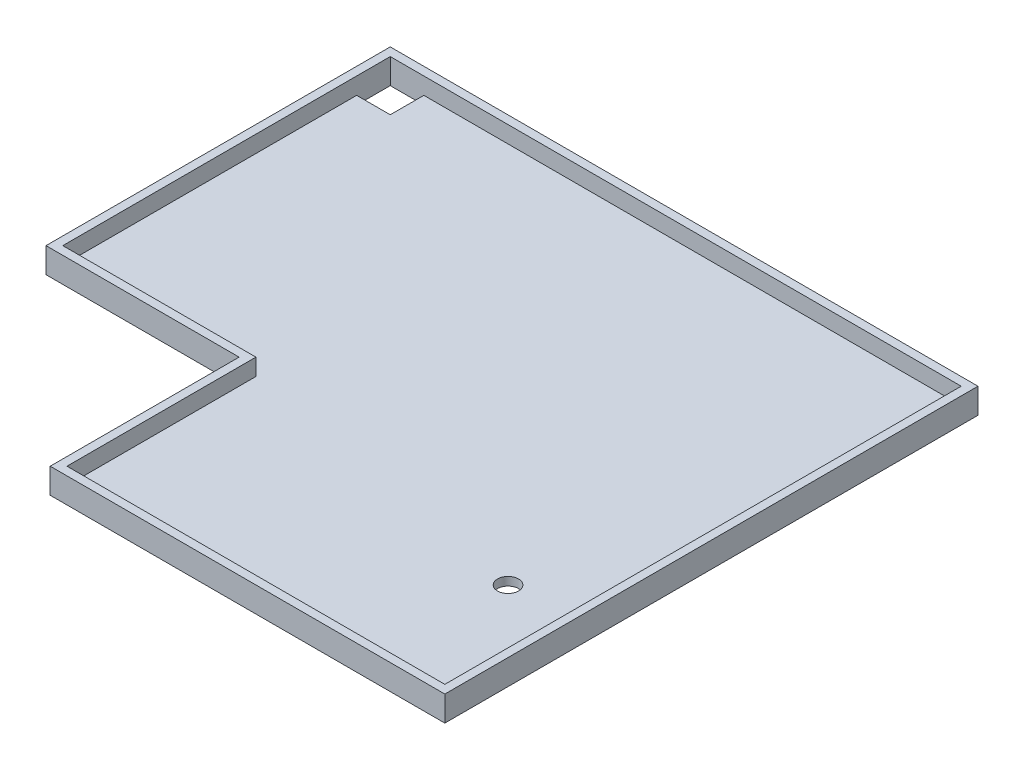
SolidWorks part; units mm, degrees
ref_plane "Front Plane" through (0, 0, 0) normal (0, 0, 1) x (1, 0, 0)
ref_plane "Top Plane" through (0, 0, 0) normal (0, 1, 0) x (1, 0, 0)
ref_plane "Right Plane" through (0, 0, 0) normal (1, 0, 0) x (0, 0, -1)
sketch "Sketch1" plane through (0, 0, 0) normal (0, 1, 0) x (1, 0, 0)
  line L0 (-34, -18) -> (-34, 19)
  line L1 (-33, -18) -> (33, -18) construction
  line L2 (-33, -18) -> (-33, 18) construction
  line L3 (-33, 18) -> (33, 18) construction
  line L4 (33, -18) -> (33, 18) construction
  line L5 (-33, -18) -> (33, 18) construction
  line L6 (-33, 18) -> (33, -18) construction
  line L7 (-10, -41.5) -> (33, -41.5) construction
  line L8 (-10, -41.5) -> (-10, -20) construction
  line L9 (-10, -20) -> (33, -20) construction
  line L10 (33, -41.5) -> (33, -20) construction
  line L11 (-10, -41.5) -> (33, -20) construction
  line L12 (-10, -20) -> (33, -41.5) construction
  line L13 (-34, 19) -> (34, 19)
  line L14 (34, -18) -> (34, 19)
  line L15 (34, -42.5) -> (34, -20)
  line L16 (-11, -42.5) -> (34, -42.5)
  line L17 (-11, -42.5) -> (-11, -20)
  line L18 (-11, -20) -> (-34, -20)
  line L19 (-34, -20) -> (-34, -18)
  line L20 (34, -18) -> (34, -20)
  line L21 (35, -18) -> (35, -20)
  line L22 (35, -43.5) -> (35, -20)
  line L23 (-12, -43.5) -> (35, -43.5)
  line L24 (-12, -43.5) -> (-12, -21)
  line L25 (-12, -21) -> (-35, -21)
  line L26 (-35, -21) -> (-35, -18)
  line L27 (-35, -18) -> (-35, 20)
  line L28 (-35, 20) -> (35, 20)
  line L29 (35, -18) -> (35, 20)
  point P0 (0, 0)
  point P5 (11.5, -30.75)
  dimension "D1" = 2
  dimension "D2" = 43
  dimension "D3" = 21.5
  dimension "D4" = 66
  dimension "D5" = 36
  dimension "D7" = 1
  dimension "D6" = 1
extrude "Boss-Extrude1" add sketch "Sketch1" along normal blind 3 contours L20 L14 L13 L0 L19 L18 L17 L16 L15 | L21 L29 L28 L27 L26 L25 L24 L23 L22 L14 L20 L15 L16 L17 L18 L19 L0 L13 region at (3.1774, 0, 8.9962) region at (34.0549, 0, 19)
extrude "Cut-Extrude2" cut sketch "Sketch1<6>" along normal through all from offset 1 contours L20 L14 L13 L0 L19 L18 L17 L16 L15 region at (3.1774, 0, 8.9962)
sketch "Sketch1<6>" plane through (0, 0, 0) normal (0, 1, 0) x (1, 0, 0) same geometry as "Sketch1"
sketch "Sketch2" plane through (0, 1, 0) normal (0, 1, 0) x (1, 0, 0)
  circle A0 centre (25.5141, -26.4861) radius 1.25
  dimension "D1" = 2.5
extrude "Cut-Extrude3" cut sketch "Sketch2" against normal through all
sketch "Sketch3" plane through (0, 1, 0) normal (0, 1, 0) x (1, 0, 0)
  line L1 (-34, 19) -> (-30, 19)
  line L2 (-34, 19) -> (-34, 15)
  line L3 (-34, 15) -> (-30, 15)
  line L4 (-30, 19) -> (-30, 15)
  dimension "D1" = 4
extrude "Cut-Extrude4" cut sketch "Sketch3" against normal up to next
